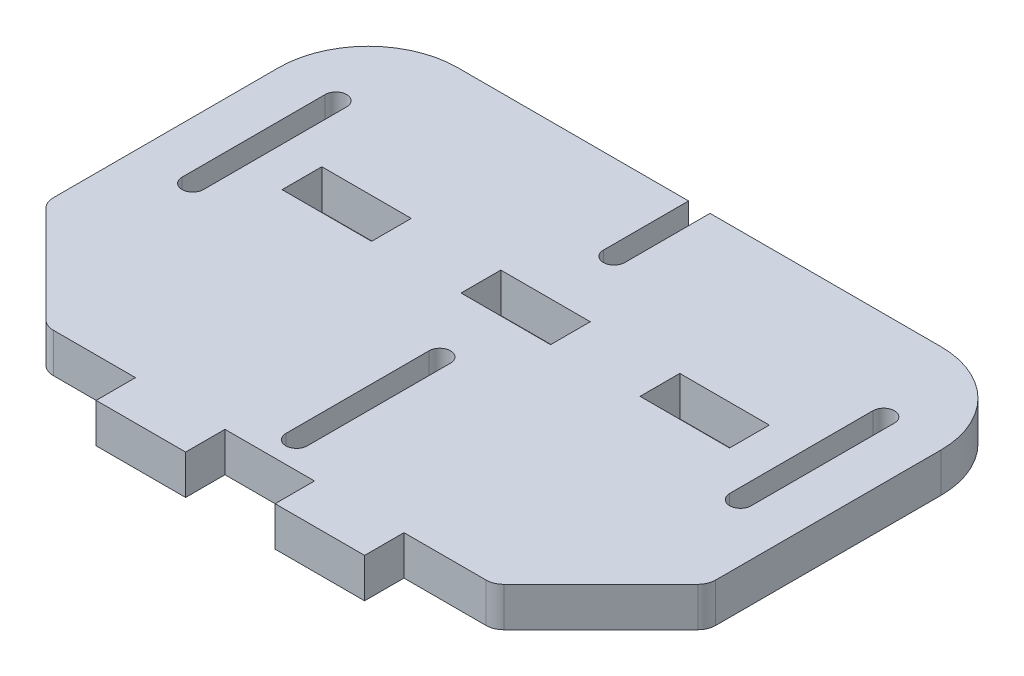
SolidWorks part; units mm, degrees
ref_plane "Front Plane" through (0, 0, 0) normal (0, 0, 1) x (1, 0, 0)
ref_plane "Top Plane" through (0, 0, 0) normal (0, 1, 0) x (1, 0, 0)
ref_plane "Right Plane" through (0, 0, 0) normal (1, 0, 0) x (0, 0, -1)
sketch "Sketch1" plane through (0, 0, 0) normal (0, 1, 0) x (1, 0, 0)
  line L8 (0, -7.5) -> (125, -7.5)
  line L12 (0, -7.5) -> (0, 3.5)
  line L14 (125, -7.5) -> (125, 3.5)
  line L17 (155, 33.5) -> (155, 123.5)
  line L18 (-30, 33.5) -> (-30, 123.5)
  line L23 (139, 58.5) -> (139, 98.5) construction
  line L24 (136, 58.5) -> (136, 98.5)
  line L25 (142, 58.5) -> (142, 98.5)
  line L26 (-14, 58.5) -> (-14, 98.5) construction
  line L27 (-17, 58.5) -> (-17, 98.5)
  line L28 (-11, 58.5) -> (-11, 98.5)
  line L29 (62.5, 11) -> (62.5, 51) construction
  line L30 (59.5, 11) -> (59.5, 51)
  line L31 (65.5, 11) -> (65.5, 51)
  line L32 (59.5, 123.5) -> (-30, 123.5)
  line L33 (65.5, 123.5) -> (65.5, 99.7057)
  line L34 (59.5, 123.5) -> (59.5, 99.7057)
  line L35 (155, 123.5) -> (65.5, 123.5)
  line L36 (125, 3.5) -> (155, 33.5)
  line L37 (0, 3.5) -> (-30, 33.5)
  arc A0 (136, 58.5) -> (142, 58.5) centre (139, 58.5) ccw
  arc A1 (142, 98.5) -> (136, 98.5) centre (139, 98.5) ccw
  arc A2 (-17, 58.5) -> (-11, 58.5) centre (-14, 58.5) ccw
  arc A3 (-11, 98.5) -> (-17, 98.5) centre (-14, 98.5) ccw
  arc A4 (59.5, 11) -> (65.5, 11) centre (62.5, 11) ccw
  arc A5 (65.5, 51) -> (59.5, 51) centre (62.5, 51) ccw
  arc A7 (59.5, 99.7057) -> (65.5, 99.7057) centre (62.5, 99.7057) ccw
  point P4 (-30, 78.5)
  point P18 (139, 78.5)
  point P23 (-14, 78.5)
  point P30 (62.5, 31)
  dimension "D7" = 16
  dimension "D8" = 45
  dimension "D9" = 3
  dimension "D10" = 40
  dimension "D13" = 16
  dimension "D1" = 89.5
  dimension "D12" = 3
  dimension "D2" = 135
  dimension "D3" = 11
  dimension "D4" = 135
  dimension "D5" = 125
  dimension "D6" = 90
extrude "Boss-Extrude6" add sketch "Sketch1" along normal blind 11
sketch "Sketch4" plane through (0, 11, 0) normal (0, 1, 0) x (1, 0, 0)
  line L0 (0, -7.5) -> (125, -7.5) construction
  line L1 (0, -7.5) -> (25, -7.5)
  line L2 (0, -7.5) -> (0, 3.5)
  line L3 (0, 3.5) -> (25, 3.5)
  line L4 (25, -7.5) -> (25, 3.5)
  line L5 (50, -7.5) -> (75, -7.5)
  line L6 (50, -7.5) -> (50, 3.5)
  line L7 (50, 3.5) -> (75, 3.5)
  line L8 (75, -7.5) -> (75, 3.5)
  line L9 (0, 69.45) -> (25, 69.45)
  line L10 (125, -7.5) -> (100, -7.5)
  line L11 (125, -7.5) -> (125, 3.5)
  line L12 (125, 3.5) -> (100, 3.5)
  line L13 (100, -7.5) -> (100, 3.5)
  line L14 (0, 69.45) -> (0, 80.55)
  line L15 (0, 80.55) -> (25, 80.55)
  line L16 (25, 69.45) -> (25, 80.55)
  line L17 (50, 69.45) -> (75, 69.45)
  line L18 (50, 69.45) -> (50, 80.55)
  line L19 (50, 80.55) -> (75, 80.55)
  line L20 (75, 69.45) -> (75, 80.55)
  line L21 (125, 69.45) -> (100, 69.45)
  line L22 (125, 69.45) -> (125, 80.55)
  line L23 (125, 80.55) -> (100, 80.55)
  line L24 (100, 69.45) -> (100, 80.55)
  point P30 (125, 75)
  dimension "D1" = 25
  dimension "D2" = 25
  dimension "D3" = 25
  dimension "D4" = 25
  dimension "D5" = 82.5
  dimension "D6" = 11.1
extrude "Cut-Extrude1" cut sketch "Sketch4" against normal through all
fillet "Fillet1" radius 25 2 edges at (155, 5.5, -123.5) (-30, 5.5, -123.5)
fillet "Fillet2" radius 5 4 edges at (155, 5.5, -33.5) (125, 5.5, -3.5) (0, 5.5, -3.5) (-30, 5.5, -33.5)
